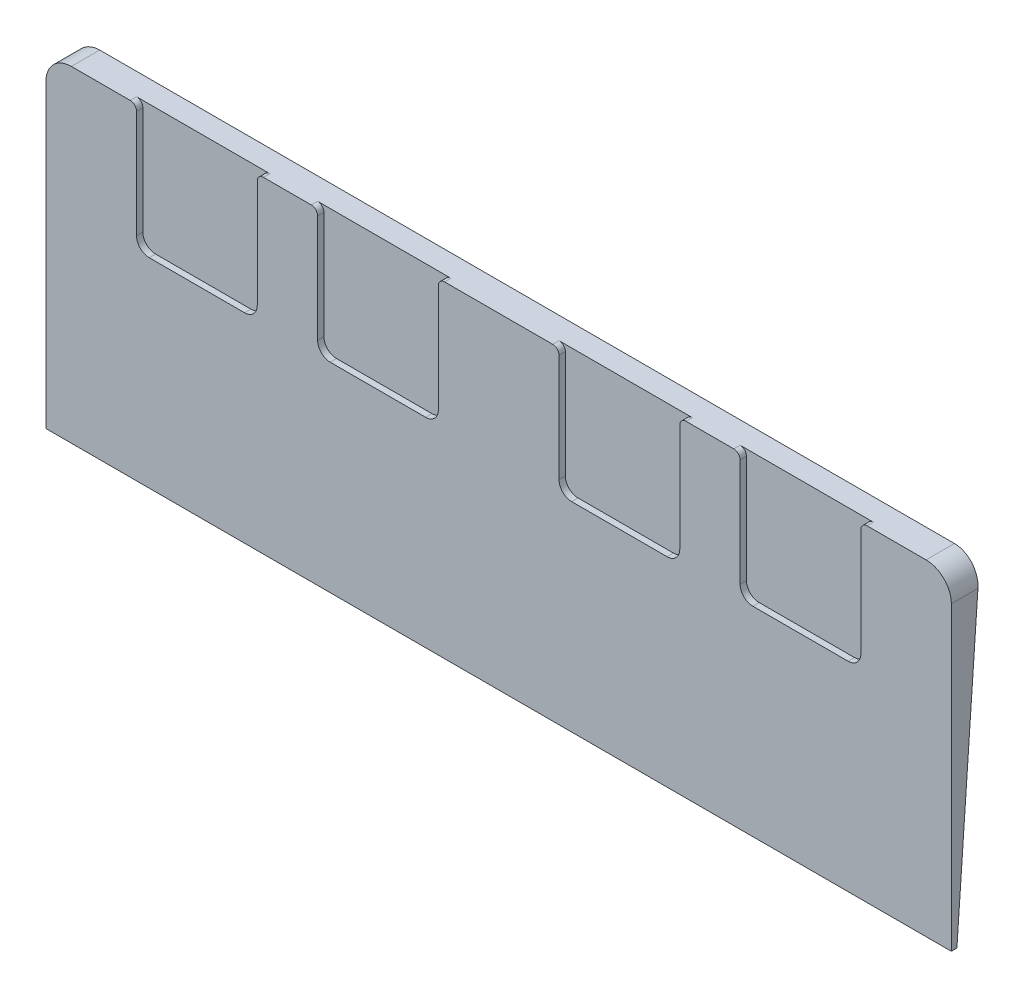
SolidWorks part; units mm, degrees
material "Glass"
ref_plane "Front Plane" through (0, 0, 0) normal (0, 0, 1) x (1, 0, 0)
ref_plane "Top Plane" through (0, 0, 0) normal (0, 1, 0) x (1, 0, 0)
ref_plane "Right Plane" through (0, 0, 0) normal (1, 0, 0) x (0, 0, -1)
ref_plane "Plane1" through (-139.7, 0, 0) normal (-1, 0, 0) x (0, 0, 1)
ref_plane "Plane2" through (146.0503, 0, 0) normal (1, 0, 0) x (0, 0, -1)
sketch "Sketch1" plane through (-139.7, 0, 0) normal (-1, 0, 0) x (0, 0, 1)
  line L2 (-4, 84.0184) -> (-4, -73.6248) construction
  line L3 (-4, -73.6248) -> (-11.2025, 29.3752)
  line L5 (14.1038, -73.6248) -> (-62.5482, -73.6248) construction
  line L6 (-4, -73.6248) -> (-15.0962, 85.0583) construction
  line L8 (-2.25, -70.6248) -> (-2.25, 29.3752)
  line L11 (-3.7435, -70.6248) -> (2.6038, -70.6248) construction
  line L14 (-2.25, -73.6248) -> (-4, -73.6248)
  line L16 (-2.25, -73.6248) -> (-2.25, -70.6248)
  line L18 (-2.25, 29.3752) -> (-11.2025, 29.3752)
  dimension "D1" = 73.6248
  dimension "D3" = 4
  dimension "D4" = 2.25
  dimension "D5" = 100
extrude "Boss-Extrude1" add sketch "Sketch1" against normal up to surface (285.7503 mm away) up to plane "Plane2"
fillet "Fillet1" radius 8 2 edges at (146.0503, 29.3752, -6.7262) (-139.7, 29.3752, -6.7262)
sketch "Sketch2" plane through (0, 0, -2.25) normal (0, 0, 1) x (1, 0, 0)
  line L0 (3.1753, 121.2498) -> (3.1753, -113.2057) construction
  line L1 (10.1748, 54.6246) -> (-3.8242, 54.6246) construction
  line L2 (60.3261, -10.6248) -> (22.2253, -10.6248)
  line L3 (-104.1252, 35.5747) -> (-118.1245, 35.5747) construction
  line L12 (-111.1249, -10.6248) -> (-111.1249, 29.3752)
  line L13 (-111.1249, 29.3752) -> (-73.0249, 29.3752)
  line L14 (-73.0249, 29.3752) -> (-73.0249, -10.6248)
  line L15 (-66.0252, 35.5747) -> (-80.0245, 35.5747) construction
  line L16 (-53.9756, -10.6248) -> (-53.9756, 29.3752)
  line L17 (-53.9756, 29.3752) -> (-15.8747, 29.3752)
  line L18 (-15.8747, 29.3752) -> (-15.8747, -10.6248)
  line L19 (-46.9752, 35.5747) -> (-60.9759, 35.5747) construction
  line L20 (-8.8752, 35.5747) -> (-22.8742, 35.5747) construction
  line L21 (-111.1249, -10.6248) -> (-73.0249, -10.6248)
  line L22 (-53.9756, -10.6248) -> (-15.8747, -10.6248)
  line L23 (117.4754, -10.6248) -> (79.3754, -10.6248)
  line L24 (22.2253, 29.3752) -> (22.2253, -10.6248)
  line L25 (60.3261, 29.3752) -> (22.2253, 29.3752)
  line L26 (60.3261, -10.6248) -> (60.3261, 29.3752)
  line L27 (79.3754, 29.3752) -> (79.3754, -10.6248)
  line L28 (117.4754, 29.3752) -> (79.3754, 29.3752)
  line L29 (117.4754, -10.6248) -> (117.4754, 29.3752)
  line L30 (138.0503, 29.3752) -> (-131.7, 29.3752) construction
  point P12 (3.1753, 54.6246)
  point P24 (-111.1249, 35.5747)
  point P27 (-73.0249, 35.5747)
  point P30 (-53.9756, 35.5747)
  point P33 (-15.8747, 35.5747)
  line M13 (138.0503, 29.3752) -> (-131.7, 29.3752)
  dimension "D1" = 40
extrude "Cut-Extrude1" cut sketch "Sketch2" against normal blind 2 contours L12 L21 L14 | L16 L22 L18 | L2 L26 L24 M13 | L23 L29 L27 M13 region at (-92.0749, 9.3752, -2.25) region at (-34.9251, 9.3752, -2.25) region at (98.4254, 9.3752, -2.25) region at (41.2757, 9.3752, -2.25)
fillet "Fillet2" radius 4 8 edges at (-15.8747, -10.6248, -3.25) (-53.9756, -10.6248, -3.25) (-111.1249, -10.6248, -3.25) (-73.0249, -10.6248, -3.25) (79.3754, -10.6248, -3.25) (117.4754, -10.6248, -3.25) (60.3261, -10.6248, -3.25) (22.2253, -10.6248, -3.25)
fillet "Fillet3" radius 2 8 edges at (117.4754, 29.3752, -3.25) (79.3754, 29.3752, -3.25) (22.2253, 29.3752, -3.25) (60.3261, 29.3752, -3.25) (-15.8747, 29.3752, -3.25) (-53.9756, 29.3752, -3.25) (-73.0249, 29.3752, -3.25) (-111.1249, 29.3752, -3.25)
